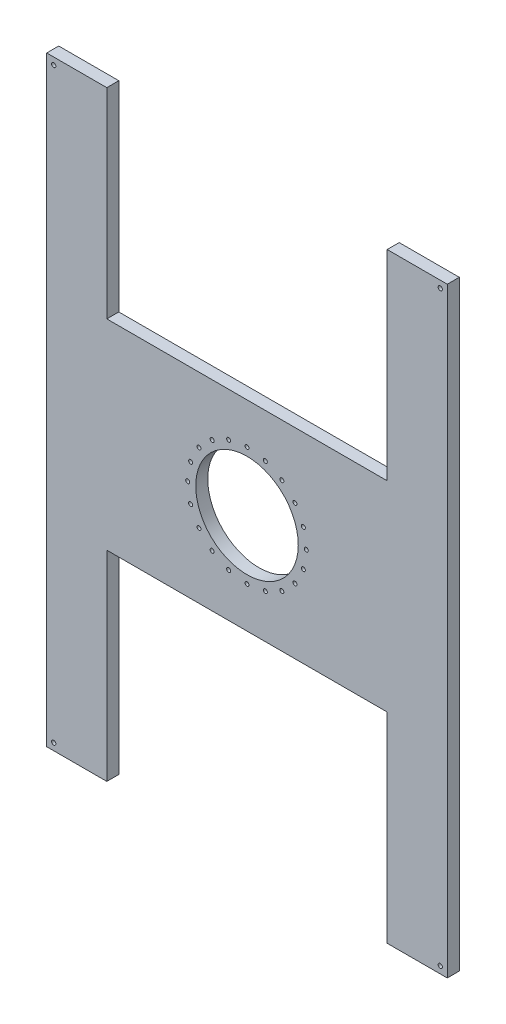
SolidWorks part; units mm, degrees
material "ASTM A36 Acier"
ref_plane "Plan de face" through (0, 0, 0) normal (0, 0, 1) x (1, 0, 0)
ref_plane "Plan de dessus" through (0, 0, 0) normal (0, 1, 0) x (1, 0, 0)
ref_plane "Plan de droite" through (0, 0, 0) normal (1, 0, 0) x (0, 0, -1)
sketch "Esquisse1" plane through (0, 0, 0) normal (0, 0, 1) x (1, 0, 0)
  line L0 (-1000, 2000) -> (-700, 2000)
  line L1 (-700, 2000) -> (-700, 1000)
  line L2 (-700, 1000) -> (700, 1000)
  line L3 (700, 1000) -> (700, 2000)
  line L4 (700, 2000) -> (1000, 2000)
  line L5 (1000, 2000) -> (1000, -1000)
  line L6 (1000, -1000) -> (700, -1000)
  line L7 (700, -1000) -> (700, 0)
  line L8 (700, 0) -> (-700, 0)
  line L9 (-700, 0) -> (-700, -1000)
  line L10 (-700, -1000) -> (-1000, -1000)
  line L11 (-1000, -1000) -> (-1000, 2000)
  point P15 (0, 0)
  dimension "D1" = 2000
  dimension "D2" = 3000
  dimension "D3" = 3000
  dimension "D4" = 300
  dimension "D5" = 300
  dimension "D6" = 300
  dimension "D7" = 300
  dimension "D8" = 1000
  dimension "D9" = 1000
  dimension "D10" = 1400
extrude "Boss.-Extru.1" add sketch "Esquisse1" along normal blind 60
sketch "Esquisse2" plane through (0, 0, 60) normal (0, 0, 1) x (1, 0, 0)
  circle A0 centre (0, 500) radius 256
  dimension "D1" = 512
  dimension "D2" = 500
extrude "Enlèv. mat.-Extru.1" cut sketch "Esquisse2" against normal through all
sketch "Esquisse4" plane through (0, 0, 0) normal (1, 0, 0) x (0, 0, -1)
  line L0 (0, 500) -> (1429.3387, 500) construction
  dimension "D1" = 500
sketch "Esquisse5" plane through (0, 0, 0) normal (0, 0, 1) x (1, 0, 0)
  circle A0 centre (0, 796) radius 10
  dimension "D1" = 20
  dimension "D2" = 296
extrude "Enlèv. mat.-Extru.3" cut sketch "Esquisse5" along normal through all
pattern_circular "Répétition circulaire1" count 20 every 18 about axis through (0, 500, 0) along (0, 0, -1) of "Enlèv. mat.-Extru.3"
ref_plane "Plan1" through (0, 0, 0) normal (0, 0, -1) x (-1, 0, 0)
sketch "Esquisse6" plane through (0, 0, 0) normal (0, 0, -1) x (-1, 0, 0)
  line L0 (-1000, 2000) -> (-700, 2000) construction
  line L1 (-1000, -1000) -> (-1000, 2000) construction
  line L2 (700, 2000) -> (1000, 2000) construction
  line L3 (1000, 2000) -> (1000, -1000) construction
  line L4 (1000, -1000) -> (700, -1000) construction
  line L5 (-700, -1000) -> (-1000, -1000) construction
  circle A0 centre (-965, 1965) radius 10.5
  circle A1 centre (-965, -965) radius 10.5
  circle A2 centre (965, -965) radius 10.5
  circle A3 centre (965, 1965) radius 10.5
  dimension "D1" = 35
  dimension "D2" = 21
  dimension "D3" = 21
  dimension "D6" = 21
  dimension "D9" = 35
  dimension "21" = 21
  dimension "35" = 35
  dimension "D4" = 35
  dimension "D5" = 35
  dimension "D7" = 35
  dimension "D8" = 35
  dimension "D10" = 35
extrude "Enlèv. mat.-Extru.4" cut sketch "Esquisse6" against normal through all
